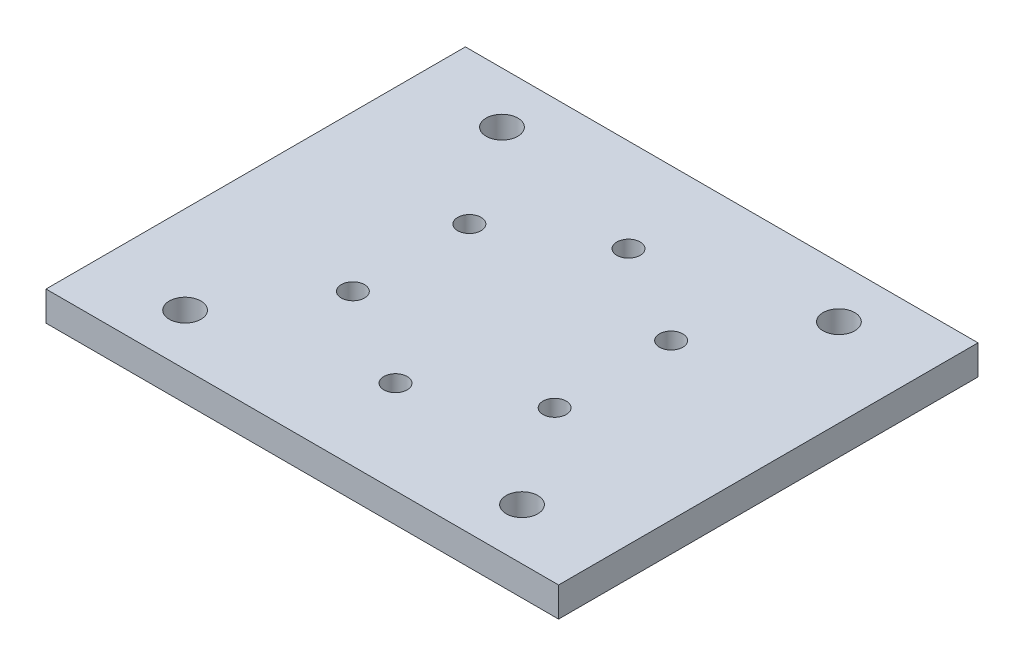
SolidWorks part; units mm, degrees
ref_plane "Front Plane" through (0, 0, 0) normal (0, 0, 1) x (1, 0, 0)
ref_plane "Top Plane" through (0, 0, 0) normal (0, 1, 0) x (1, 0, 0)
ref_plane "Right Plane" through (0, 0, 0) normal (1, 0, 0) x (0, 0, -1)
sketch "Sketch2" plane through (0, 0, 0) normal (0, 1, 0) x (1, 0, 0)
  line L0 (0, 0) -> (0, 90)
  line L1 (0, 90) -> (110, 90)
  line L2 (110, 90) -> (110, 0)
  line L3 (110, 0) -> (0, 0)
  dimension "D1" = 110
  dimension "D2" = 90
extrude "Boss-Extrude1" add sketch "Sketch2" along normal blind 6.35
sketch "Sketch3" plane through (0, 6.35, 0) normal (0, 1, 0) x (1, 0, 0)
  line L1 (110, 90) -> (0, 90) construction
  line L2 (0, 0) -> (110, 0) construction
  line L4 (55, 90) -> (55, 0) construction
  line L5 (0, 45) -> (55, 45) construction
  line L6 (55, 45) -> (110, 45) construction
  line L7 (0, 90) -> (0, 0) construction
  circle A0 centre (18.85, 79) radius 3.4
  circle A1 centre (18.85, 11) radius 3.4
  circle A2 centre (91.15, 11) radius 3.4
  circle A3 centre (91.15, 79) radius 3.4
  dimension "D4" = 6.8
  dimension "D3" = 11
  dimension "D2" = 18.85
extrude "Mounting Holes" cut sketch "Sketch3" against normal through all
sketch "Sketch4" plane through (0, 6.35, 0) normal (0, 1, 0) x (1, 0, 0)
  line L0 (18.85, 79) -> (91.15, 11) construction
  circle A0 centre (55, 45) radius 25 construction
  circle A1 centre (55, 70) radius 2.5
  circle A2 centre (76.6506, 57.5) radius 2.5
  circle A3 centre (76.6506, 32.5) radius 2.5
  circle A4 centre (55, 20) radius 2.5
  circle A5 centre (33.3494, 32.5) radius 2.5
  circle A6 centre (33.3494, 57.5) radius 2.5
  point P20 (55, 45)
  dimension "D1" = 50
  dimension "D2" = 5
  dimension "D3" = 6
extrude "Cut-Extrude1" cut sketch "Sketch4" against normal through all
sketch "Sketch5" plane through (0, 6.35, 0) normal (0, 1, 0) x (1, 0, 0)
  circle A0 centre (55, 45) radius 25 construction
  circle A1 centre (55, 20) radius 2.5 construction
  circle A2 centre (55, 20) radius 2.5 construction
  circle A3 centre (33.3494, 32.5) radius 2.5 construction
  circle A4 centre (33.3494, 32.5) radius 2.5 construction
  circle A5 centre (33.3494, 57.5) radius 2.5 construction
  circle A6 centre (33.3494, 57.5) radius 2.5 construction
equation "\"L1L\"=500"
equation "\"L1Thick\"=6.35"
equation "\"Harm-Drive-Outer\"=74.5"
equation "\"L1-Spacing\"=100"
equation "\"L-Bracket-HoleToWall\"=12.5"
equation "\"D3@Sketch3\"=\"L-Bracket-HoleToSide\""
equation "\"L-Bracket-HoleToSide\"=11"
equation "\"Bracket-Hole-D\"=6.8"
equation "\"D4@Sketch3\"=\"Bracket-Hole-D\""
equation "\"L1-Spacing\"=115.65"
equation "\"D2@Sketch3\"=\"L-Bracket-HoleToWall\"+\"L1Thick\""
